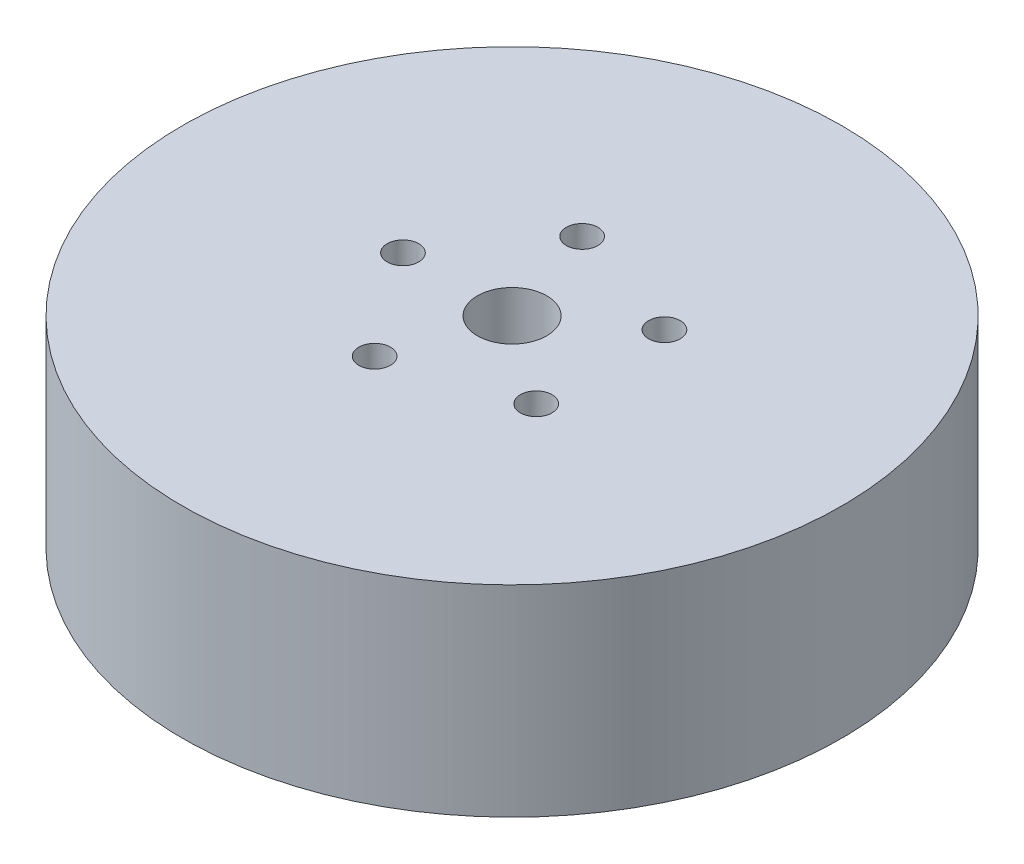
SolidWorks part; units mm, degrees
ref_plane "Front Plane" through (0, 0, 0) normal (0, 0, 1) x (1, 0, 0)
ref_plane "Top Plane" through (0, 0, 0) normal (0, 1, 0) x (1, 0, 0)
ref_plane "Right Plane" through (0, 0, 0) normal (1, 0, 0) x (0, 0, -1)
sketch "Sketch1" plane through (0, 0, 0) normal (0, 1, 0) x (1, 0, 0)
  circle A0 centre (0, 0) radius 47.5
  dimension "FLANGE_OD" = 95
extrude "Boss-Extrude1" add sketch "Sketch1" along normal blind 29
sketch "Sketch2" plane through (0, 0, 0) normal (0, 1, 0) x (1, 0, 0)
  circle A0 centre (0, 0) radius 5
  dimension "BORE_D" = 10
extrude "Cut-Extrude1" cut sketch "Sketch2" along normal through all
sketch "Sketch3" plane through (0, 29, 0) normal (0, 1, 0) x (1, 0, 0)
  circle A0 centre (0, 0) radius 15.7237 construction
  circle A1 centre (-15.7237, 0) radius 2.2799
  dimension "BOLT_D" = 4.5598
  dimension "BOLT_PCD" = 31.4473
extrude "Cut-Extrude2" cut sketch "Sketch3" against normal blind 27.3605
pattern_circular "CirPattern1" count 5 over 360 about axis through (0, 0, 0) along (0, 1, 0) of "Cut-Extrude2"
